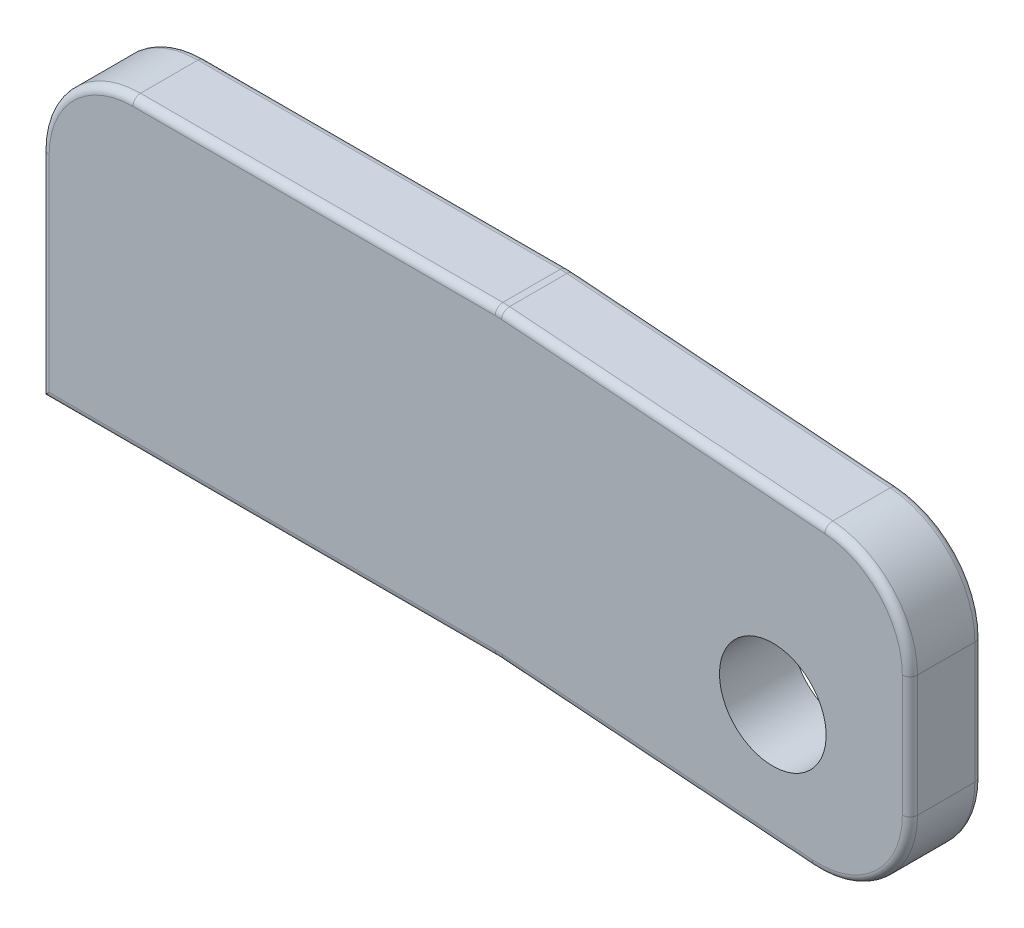
SolidWorks part; units mm, degrees
material "6061-T6 (SS)"
ref_plane "Front Plane" through (0, 0, 0) normal (0, 0, 1) x (1, 0, 0)
ref_plane "Top Plane" through (0, 0, 0) normal (0, 1, 0) x (1, 0, 0)
ref_plane "Right Plane" through (0, 0, 0) normal (1, 0, 0) x (0, 0, -1)
sketch "Sketch1" plane through (0, 0, 0) normal (0, 0, 1) x (1, 0, 0)
  line L0 (114, 13) -> (96, 13) construction
  line L1 (0, 0) -> (60, 0)
  line L2 (0, 0) -> (0, 40)
  line L3 (0, 40) -> (60, 40)
  line L4 (114, -4) -> (114, 36)
  line L5 (60, 40) -> (60, 0) construction
  line L7 (60, 0) -> (114, -4)
  line L8 (60, 40) -> (114, 36)
  circle A0 centre (96, 13) radius 7
  dimension "D3" = 14
  dimension "D1" = 40
  dimension "D2" = 60
  dimension "D4" = 40
  dimension "D5" = 4
  dimension "D6" = 13
  dimension "D7" = 114
  dimension "D8" = 18
extrude "Boss-Extrude1" add sketch "Sketch1" along normal blind 9.525
fillet "Fillet1" radius 12 5 edges at (0, 40, 4.7625) (60, 0, 4.7625) (114, -4, 4.7625) (114, 36, 4.7625) (60, 40, 4.7625)
sketch "Sketch2" plane through (0, 0, 0) normal (0, 1, 0) x (1, 0, 0)
  line L0 (0, 0) -> (0, 23.2153)
  line L1 (0, -12.7625) -> (0, 371.2375) construction
  line L2 (0, 23.2153) -> (48, 23.2153)
  line L3 (48, 371.2375) -> (48, -12.7625) construction
  line L4 (48, 23.2153) -> (48, 0)
  line L5 (59.5562, 0) -> (12, 0) construction
  line L6 (0, 0) -> (48, 0)
  circle A5 centre (40, 19.2375) radius 2
  circle A6 centre (8, 19.2375) radius 2
  circle A7 centre (8, 3.2375) radius 2
  circle A8 centre (40, 3.2375) radius 2
extrude "Boss-Extrude3" add sketch "Sketch2" along normal blind 5
fillet "Fillet5" radius 1 30 edges at (48, 0, -11.6076) (53.7781, 0, 0) (59.9997, -0.0082, 0) (80.7781, -1.5391, 0) (110.1659, 0.1287, 0) (114, 16.8889, 0) (110.7931, 33.0219, 0) (81.6645, 38.3952, 0) (59.9997, 39.9918, 0) (35.7781, 40, 0) (3.5147, 36.4853, 0) (0, 16.5, 0) (48, 2.5, 0) (29.7781, 0, 9.525) (59.9997, -0.0082, 9.525) (80.7781, -1.5391, 9.525) (110.1659, 0.1287, 9.525) (114, 16.8889, 9.525) (110.7931, 33.0219, 9.525) (81.6645, 38.3952, 9.525) (59.9997, 39.9918, 9.525) (35.7781, 40, 9.525) (0, 14, 9.525) (3.5147, 36.4853, 9.525) (0, 5, -11.6076) (0, 2.5, -23.2153) (48, 2.5, -23.2153) (24, 5, -23.2153) (48, 5, -11.6076) (24, 5, 0)
sketch "Sketch4" plane through (0, 5, 0) normal (0, 1, 0) x (1, 0, 0)
  line L0 (47, 22.2153) -> (1, 22.2153) construction
  point P0 (24, 22.2153)
ref_plane "Plane1" through (24, 0, 0) normal (1, 0, 0) x (0, 0, -1)
sketch "Sketch5" plane through (24, 0, 0) normal (1, 0, 0) x (0, 0, -1)
  line L0 (22.2153, 5) -> (0, 39)
rib "Rib3" sketch "Sketch5" sketch "Sketch5" thickness 10 extrusion direction parallel to sketch draft on no parameters "D1"=10
fillet "Fillet6" radius 1 6 edges at (29, 22.5, 0) (29, 5.2929, -0.2929) (19, 22.5, 0) (19, 5.2929, -0.2929) (29, 5, -11.6076) (19, 5, -11.6076)
fillet "Fillet7" radius 1 6 edges at (18.7071, 5.2929, -22.0239) (18.7071, 38.5517, -0.2929) (29.2929, 5.2929, -22.0239) (29.2929, 38.5517, -0.2929) (19, 21.7348, -11.281) (29, 21.7348, -11.281)
